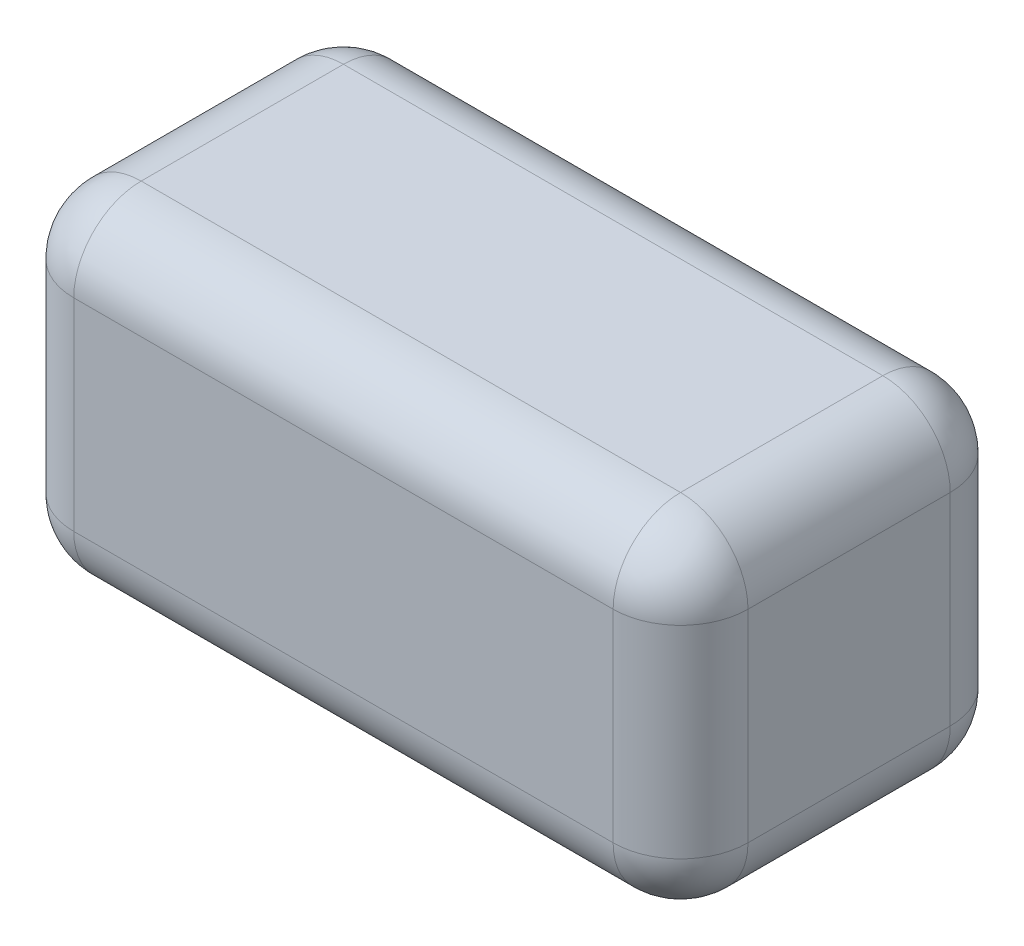
SolidWorks part; units mm, degrees
ref_plane "Front Plane" through (0, 0, 0) normal (0, 0, 1) x (1, 0, 0)
ref_plane "Top Plane" through (0, 0, 0) normal (0, 1, 0) x (1, 0, 0)
ref_plane "Right Plane" through (0, 0, 0) normal (1, 0, 0) x (0, 0, -1)
sketch "Sketch1" plane through (0, 0, 0) normal (0, 1, 0) x (1, 0, 0)
  line L1 (50, 25) -> (-50, 25)
  line L2 (50, 25) -> (50, -25)
  line L3 (50, -25) -> (-50, -25)
  line L4 (-50, 25) -> (-50, -25)
  line L5 (50, 25) -> (-50, -25) construction
  line L6 (50, -25) -> (-50, 25) construction
  point P0 (0, 0)
  dimension "D1" = 50
  dimension "D2" = 100
extrude "Boss-Extrude1" add sketch "Sketch1" along normal blind 50
fillet "Fillet1" radius 10 9 edges at (50, 25, -25) (50, 0, 0) (0, 50, -25) (50, 50, 0) (-50, 50, 0) (-50, 25, 25) (0, 50, 25) (50, 25, 25) (0, 0, 25)
fillet "Fillet2" radius 10 6 edges at (47.0711, 2.9289, -22.0711) (-47.0711, 2.9289, 22.0711) (-47.0711, 47.0711, -22.0711) (-50, 20, -25) (-50, 0, -5) (-5, 0, -25)
